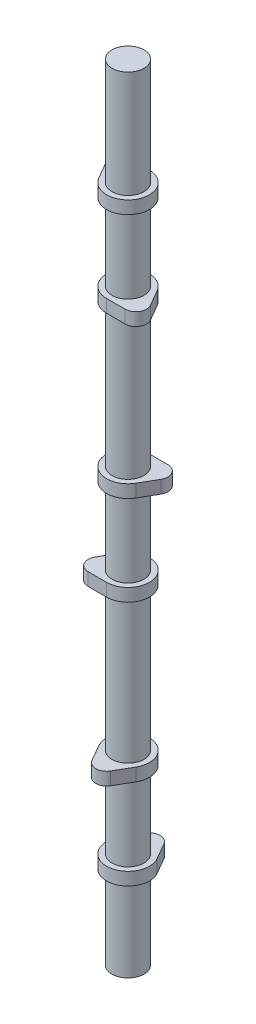
SolidWorks part; units mm, degrees
ref_plane "Front Plane" through (0, 0, 0) normal (0, 0, 1) x (1, 0, 0)
ref_plane "Top Plane" through (0, 0, 0) normal (0, 1, 0) x (1, 0, 0)
ref_plane "Right Plane" through (0, 0, 0) normal (1, 0, 0) x (0, 0, -1)
sketch "Sketch3" plane through (0, 0, 0) normal (0, 1, 0) x (1, 0, 0)
  line L0 (-5.4993, 15.875) -> (-10.9985, 6.35)
  line L1 (5.4993, 15.875) -> (10.9985, 6.35)
  arc A0 (-10.9985, 6.35) -> (10.9985, 6.35) centre (0, 0) ccw
  arc A1 (5.4993, 15.875) -> (-5.4993, 15.875) centre (0, 12.7) ccw
  dimension "D2" = 12.7
  dimension "D3" = 25.4
  dimension "D1" = 12.7
extrude "Boss-Extrude1" add sketch "Sketch3" along normal blind 7.62
ref_axis "Axis1" through (0, 64.2303, 0) along (0, -1, 0)
pattern_linear "LPattern2" count 2 spacing 53.34 along (0, 1, 0) of "Boss-Extrude1"
move or copy body "Body-Move/Copy1" bodies to move or copy 103 copy no rotation origin (0, 0, 0) rotation axis (0, 1, 0) rotation angle 180
pattern_linear "LPattern3" count 3 spacing 146.05 along (0, 1, 0) of bodies 101 104
move or copy body "Body-Move/Copy2" bodies to move or copy 105 107 copy no rotation origin (0, 0, 0) rotation axis (0, 1, 0) rotation angle 120
move or copy body "Body-Move/Copy3" bodies to move or copy 108 106 copy no rotation origin (0, 0, 0) rotation axis (0, -1, 0) rotation angle 120
sketch "Sketch4" plane through (0, 0, 0) normal (0, 1, 0) x (1, 0, 0)
  circle A0 centre (0, 0) radius 9.5
  dimension "D1" = 19
extrude "Boss-Extrude2" add sketch "Sketch4" along normal blind 466.09 from offset 49.53 offset against normal yes
